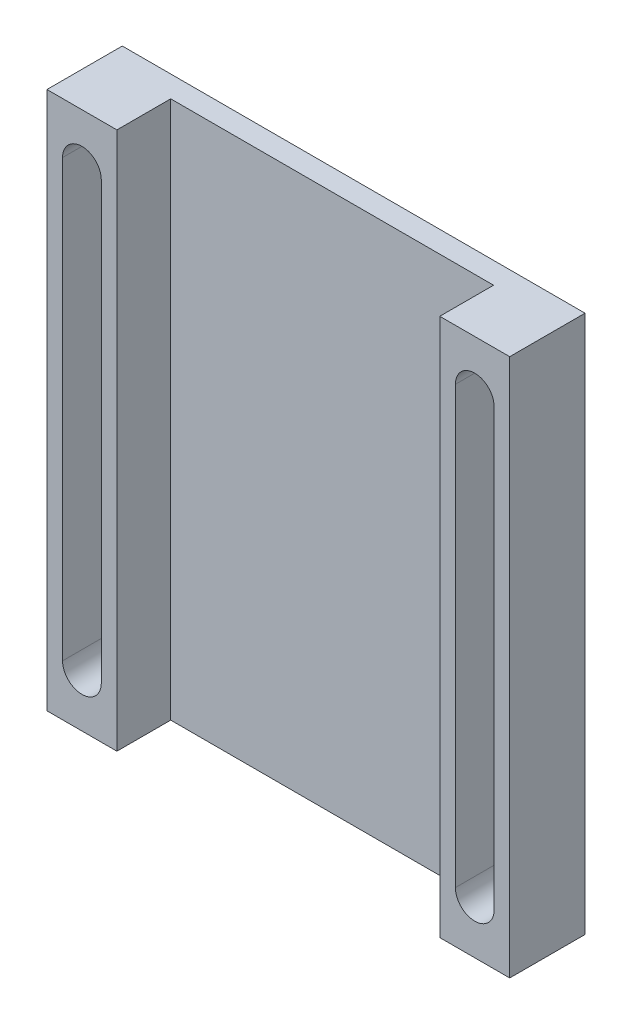
SolidWorks part; units mm, degrees
ref_plane "Front Plane" through (0, 0, 0) normal (0, 0, 1) x (1, 0, 0)
ref_plane "Top Plane" through (0, 0, 0) normal (0, 1, 0) x (1, 0, 0)
ref_plane "Right Plane" through (0, 0, 0) normal (1, 0, 0) x (0, 0, -1)
sketch "Sketch1" plane through (0, 0, 0) normal (0, 0, 1) x (1, 0, 0)
  line L0 (150, 250) -> (150, -250)
  line L3 (-215, 250) -> (-215, -250)
  line L4 (-215, -250) -> (215, -250)
  line L5 (215, 250) -> (215, -250)
  line L6 (-150, 250) -> (-150, -250)
  line L7 (0, 250) -> (0, -250) construction
  line L8 (-182.5, 202.5) -> (-182.5, -202.5) construction
  line L9 (-164.5, 202.5) -> (-164.5, -202.5)
  line L10 (-200.5, 202.5) -> (-200.5, -202.5)
  line L11 (182.5, 202.5) -> (182.5, -202.5) construction
  line L12 (164.5, 202.5) -> (164.5, -202.5)
  line L13 (200.5, 202.5) -> (200.5, -202.5)
  line L14 (-215, 250) -> (-150, 250) construction
  line L15 (-215, 250) -> (215, 250)
  arc A2 (-164.5, 202.5) -> (-200.5, 202.5) centre (-182.5, 202.5) ccw
  arc A3 (-200.5, -202.5) -> (-164.5, -202.5) centre (-182.5, -202.5) ccw
  arc A4 (164.5, 202.5) -> (200.5, 202.5) centre (182.5, 202.5) cw
  arc A5 (200.5, -202.5) -> (164.5, -202.5) centre (182.5, -202.5) cw
  point P4 (-182.5, 250)
  point P16 (-182.5, 0)
  point P23 (182.5, 0)
  point P28 (150, 0)
  point P29 (0, 0)
  dimension "D5" = 18
  dimension "D1" = 430
  dimension "D2" = 500
  dimension "D3" = 65
  dimension "D4" = 405
extrude "Boss-Extrude1" add sketch "Sketch1" along normal blind 20 contours L15 L6 L4 L0 region at (0, 0, 0)
extrude "Boss-Extrude2" add sketch "Sketch1<3>" along normal blind 70 contours L15 L0 L4 L5 L13 A5 L12 A4 | A5 L13 A4 L12 | L15 L3 L4 L6 A3 L10 A2 L9 | L9 A3 L10 A2 region at (182.5, 244.9579, 0) region at (-155.0421, 0, 0) region at (182.5, 0, 0)
sketch "Sketch1<3>" plane through (0, 0, 0) normal (0, 0, 1) x (1, 0, 0) same geometry as "Sketch1"
extrude "Cut-Extrude1" cut sketch "Sketch1<5>" against normal blind 47 from surface contours L10 A3 L9 A2 | L13 A5 L12 A4 starting at face at (-182.5, 0, 70)
sketch "Sketch1<5>" plane through (0, 0, 0) normal (0, 0, 1) x (1, 0, 0) same geometry as "Sketch1"
